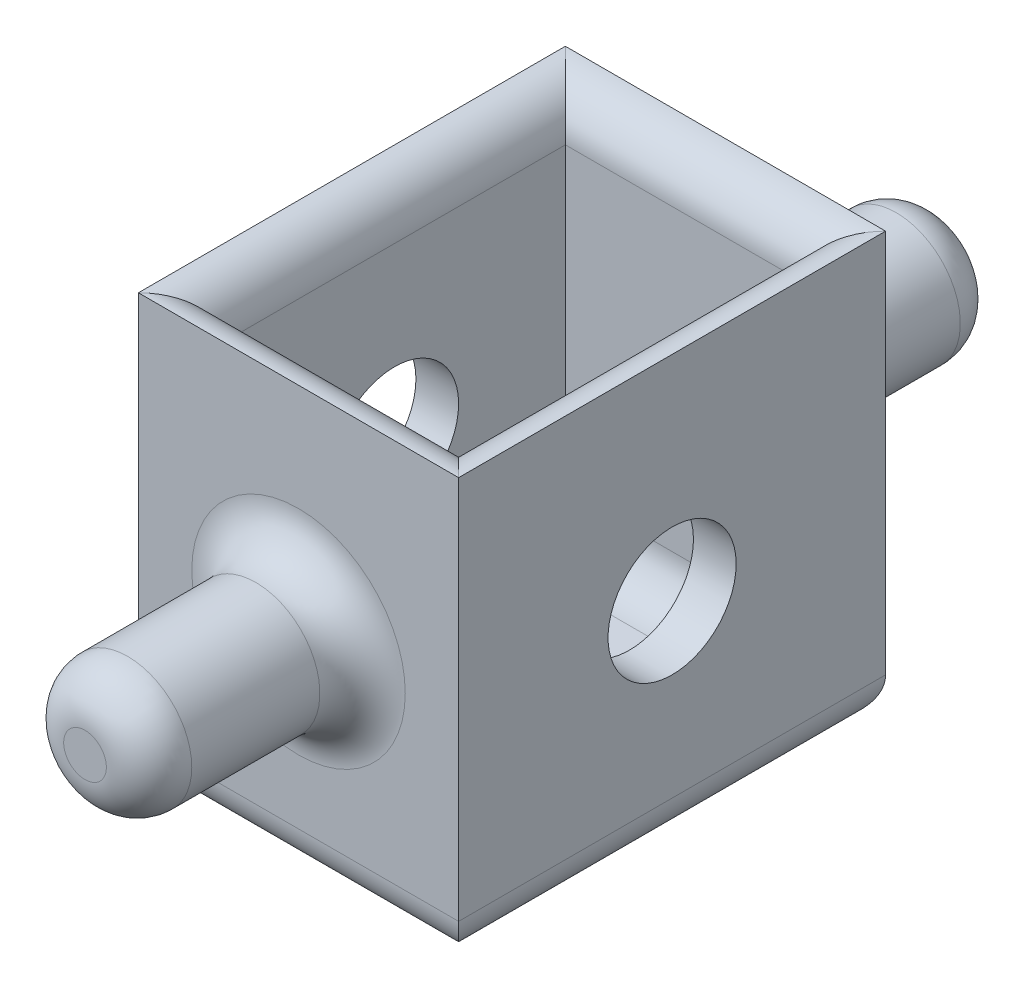
SolidWorks part; units mm, degrees
ref_plane "Front Plane" through (0, 0, 0) normal (0, 0, 1) x (1, 0, 0)
ref_plane "Top Plane" through (0, 0, 0) normal (0, 1, 0) x (1, 0, 0)
ref_plane "Right Plane" through (0, 0, 0) normal (1, 0, 0) x (0, 0, -1)
sketch "Sketch1" plane through (0, 0, 0) normal (0, 0, 1) x (1, 0, 0)
  line L1 (-9.525, -12.7) -> (9.525, -12.7)
  line L2 (-9.525, -12.7) -> (-9.525, 12.7)
  line L3 (-9.525, 12.7) -> (9.525, 12.7)
  line L4 (9.525, -12.7) -> (9.525, 12.7)
  line L5 (-9.525, -12.7) -> (9.525, 12.7) construction
  line L6 (-9.525, 12.7) -> (9.525, -12.7) construction
  point P0 (0, 0)
  dimension "D1" = 19.05
  dimension "D2" = 25.4
extrude "main body" add sketch "Sketch1" along normal blind 25.4
shell "hollow it" thickness 2.54 removed face at (0, 12.7, 12.7)
ref_point "cut point"
sketch "Sketch2" plane through (9.525, 0, 0) normal (1, 0, 0) x (0, 0, -1)
  circle A0 centre (-12.7, 0) radius 3.81
  dimension "D1" = 0
  dimension "D2" = 12.7
ref_point "bigger nibble point"
ref_point "bigger nibble here, too"
sketch "Sketch3" plane through (0, 0, 25.4) normal (0, 0, 1) x (1, 0, 0)
  circle A0 centre (0, 0) radius 3.81
  dimension "D1" = 7.62
extrude "nibble no 1" add sketch "Sketch3" along normal blind 12.7
sketch "Sketch4" plane through (0, 0, 0) normal (0, 0, -1) x (-1, 0, 0)
  circle A0 centre (0, 0) radius 3.81
  dimension "D1" = 7.62
extrude "nibble no 2" add sketch "Sketch4" along normal blind 12.7
ref_point "nibble center"
ref_plane "nibble flag plane" through (0, 0, 0) normal (0, -1, 0) x (-1, 0, 0)
sketch "Sketch5" plane through (0, 0, 0) normal (0, -1, 0) x (-1, 0, 0)
  line L1 (-0.8217, 4.4483) -> (0.4483, 4.4483)
  line L2 (-0.8217, 4.4483) -> (-0.8217, 8.2583)
  line L3 (-0.8217, 8.2583) -> (0.4483, 8.2583)
  line L4 (0.4483, 4.4483) -> (0.4483, 8.2583)
  line L5 (-0.8217, 4.4483) -> (0.4483, 8.2583) construction
  line L6 (-0.8217, 8.2583) -> (0.4483, 4.4483) construction
  point P0 (-0.1867, 6.3533)
  dimension "D1" = 1.27
  dimension "D2" = 3.81
extrude "flag" add sketch "Sketch5" along normal blind 0.254
extrude "nibble holes" cut sketch "Sketch2" against normal through all
fillet "smoothness" radius 2.54 16 edges at (-9.525, -12.7, 12.7) (0, -12.7, 25.4) (9.525, -12.7, 12.7) (0, -12.7, 0) (6.985, -10.16, 12.7) (0, -10.16, 22.86) (-6.985, -10.16, 12.7) (0, -10.16, 2.54) (-3.81, 0, 0) (-3.81, 0, -12.7) (-6.985, 12.7, 12.7) (0, 12.7, 2.54) (6.985, 12.7, 12.7) (0, 12.7, 22.86) (3.81, 0, 38.1) (-3.81, 0, 25.4)
